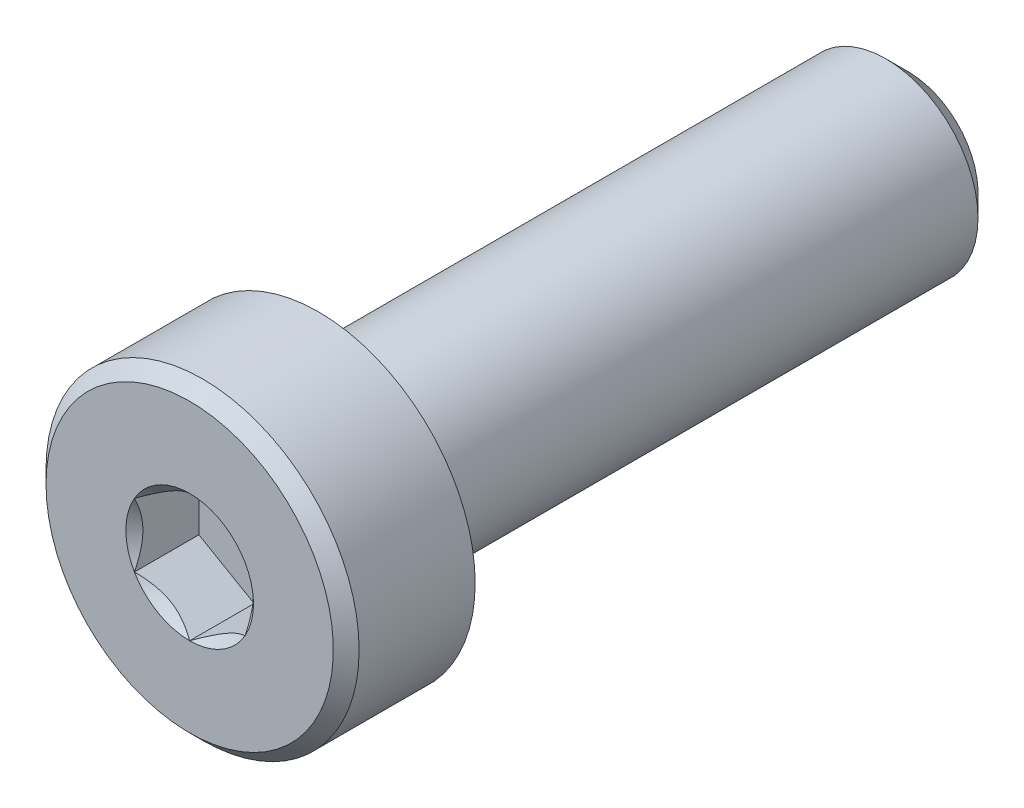
SolidWorks part; units mm, degrees
ref_plane "Front Plane" through (0, 0, 0) normal (0, 0, 1) x (1, 0, 0)
ref_plane "Top Plane" through (0, 0, 0) normal (0, 1, 0) x (1, 0, 0)
ref_plane "Right Plane" through (0, 0, 0) normal (1, 0, 0) x (0, 0, -1)
sketch "Sketch1" plane through (0, 0, 0) normal (1, 0, 0) x (0, 0, -1)
  line L0 (-9.75, 0) -> (9.75, 0) construction
  line L1 (-9.75, 0) -> (-9.75, 4.25)
  line L2 (-9.75, 4.25) -> (-6.25, 4.25)
  line L3 (-6.25, 4.25) -> (-6.25, 2.5)
  line L4 (-6.25, 2.5) -> (9.75, 2.5)
  line L5 (9.75, 2.5) -> (9.75, 0)
  line L6 (-9.75, 3.9) -> (-9.4, 4.25)
  line L7 (9.7, 2.5866) -> (10.1, 1.8938) construction
  line L8 (10.1, 1.8938) -> (10.5, 2.5866) construction
  line L9 (10.5, 2.5866) -> (9.7, 2.5866) construction
  line L10 (9.725, 2.5433) -> (10.475, 2.5433)
  line L11 (10.475, 2.5433) -> (10.15, 1.9804)
  line L12 (10.15, 1.9804) -> (10.05, 1.9804)
  line L13 (10.05, 1.9804) -> (9.725, 2.5433)
  line L14 (10.1, 1.9804) -> (10.1, 1.8938) construction
  line L15 (9.75, 2.5) -> (10.45, 2.5) construction
  line L16 (10.1, 2.5866) -> (10.1, 2.5) construction
  line L17 (9.15, 2.5) -> (9.75, 1.9)
  line L18 (-6.25, -2.5) -> (9.75, -2.5)
  point P2 (0, 0)
  point P22 (10.1, 2.5433)
  point P23 (-8, 0)
  point P27 (6.95, -2.5)
  dimension "Head Height" = 3.5
  dimension "Length" = 16
  dimension "Head Diameter" = 8.5
  dimension "Thread Size" = 5
  dimension "D1" = 45
  dimension "Thread Pitch" = 0.8
  dimension "D3" = 0.1
  dimension "D2" = 45
  dimension "D4" = 0.6
  dimension "D5" = 1.75
  dimension "D6" = 2.8
  dimension "D7" = 0.35
sketch "Sketch3" plane through (0, 0, 0) normal (0, 0, 1) x (1, 0, 0)
  line L1 (0, 1.7321) -> (-1.5, 0.866)
  line L2 (-1.5, 0.866) -> (-1.5, -0.866)
  line L3 (-1.5, -0.866) -> (0, -1.7321)
  line L4 (0, -1.7321) -> (1.5, -0.866)
  line L5 (1.5, -0.866) -> (1.5, 0.866)
  line L6 (1.5, 0.866) -> (0, 1.7321)
  circle A0 centre (0, 0) radius 1.5 construction
  dimension "Drive Size" = 3
sketch "Sketch2" plane through (0, 0, 0) normal (1, 0, 0) x (0, 0, -1)
  line L0 (-9.75, 0) -> (-9.75, 3.9)
  line L1 (-9.75, 3.9) -> (-9.4, 4.25)
  line L2 (-9.4, 4.25) -> (-6.25, 4.25)
  line L3 (-6.25, 4.25) -> (-6.25, 2.5)
  line L4 (-6.25, 2.5) -> (9.15, 2.5)
  line L5 (9.15, 2.5) -> (9.75, 1.9)
  line L6 (9.75, 1.9) -> (9.75, 0)
  line L7 (9.75, 0) -> (-9.75, 0)
revolve "Revolve1" add sketch "Sketch2" angle 360 about L7
sketch "Sketch4" plane through (0, 0, 9.75) normal (0, 0, 1) x (1, 0, 0)
  line L0 (1.5, -0.866) -> (1.5, 0.866) construction
  line L1 (0, -1.7321) -> (1.5, -0.866) construction
  line L2 (-1.5, -0.866) -> (0, -1.7321) construction
  line L3 (-1.5, 0.866) -> (-1.5, -0.866) construction
  line L4 (0, 1.7321) -> (-1.5, 0.866) construction
  line L5 (1.5, 0.866) -> (0, 1.7321) construction
  line L6 (1.5, -0.866) -> (1.5, 0.866)
  line L7 (0, -1.7321) -> (1.5, -0.866)
  line L8 (-1.5, -0.866) -> (0, -1.7321)
  line L9 (-1.5, 0.866) -> (-1.5, -0.866)
  line L10 (0, 1.7321) -> (-1.5, 0.866)
  line L11 (1.5, 0.866) -> (0, 1.7321)
extrude "Cut-Extrude1" cut sketch "Sketch4" against normal up to vertex (1.75 mm away) up to point (0, 0, 8)
sketch "Sketch5" plane through (0, 0, 9.75) normal (0, 0, 1) x (1, 0, 0)
  circle A0 centre (0, 0) radius 1.7321
extrude "Cut-Extrude2" cut sketch "Sketch5" against normal up to vertex (1.75 mm away) draft 45 up to point (0, 0, 8)
split "Split1" [suppressed] bodies to split 106
sketch "Sketch6" plane through (0, 0, -9.75) normal (0, 0, -1) x (-1, 0, 0)
  circle A0 centre (0, 0) radius 2.5 construction
  circle A1 centre (0, 0) radius 2.5
curve "Helix/Spiral1" [suppressed] pitch 0.8 height 16.8 turns 21
sketch "Sketch7" plane through (0, 0, 0) normal (1, 0, 0) x (0, 0, -1)
  line L0 (9.725, 2.5433) -> (10.475, 2.5433) construction
  line L1 (10.05, 1.9804) -> (9.725, 2.5433) construction
  line L2 (10.15, 1.9804) -> (10.05, 1.9804) construction
  line L3 (10.475, 2.5433) -> (10.15, 1.9804) construction
  line L4 (9.725, 2.5433) -> (10.475, 2.5433)
  line L5 (10.05, 1.9804) -> (9.725, 2.5433)
  line L6 (10.15, 1.9804) -> (10.05, 1.9804)
  line L7 (10.475, 2.5433) -> (10.15, 1.9804)
sweep "Cut-Sweep1" [suppressed] cut profiles "Sketch7" path "Helix/Spiral1"
sketch "Sketch8" plane through (0, 0, 6.25) normal (0, 0, -1) x (-1, 0, 0)
  circle A0 centre (0, 0) radius 2.5
extrude "Boss-Extrude1" [suppressed] add sketch "Sketch8" along normal up to vertex draft 30.9
equation "\"D3@Sketch1\" = \"Thread Pitch@Sketch1\" / 8"
equation "\"D4@Sketch1\" = \"Thread Pitch@Sketch1\" * .75"
equation "\"D5@Sketch1\"=\"Head Height@Sketch1\"*0.5"
equation "\"D4@Helix/Spiral1\" = \"Thread Pitch@Sketch1\""
equation "\"D3@Helix/Spiral1\" = \"Thread Pitch@Sketch1\" + \"Length@Sketch1\""
equation "\"D6@Sketch1\"=\"Thread Pitch@Sketch1\" * 3.5"
equation "\"D7@Sketch1\"=\"Head Height@Sketch1\"*.1"
